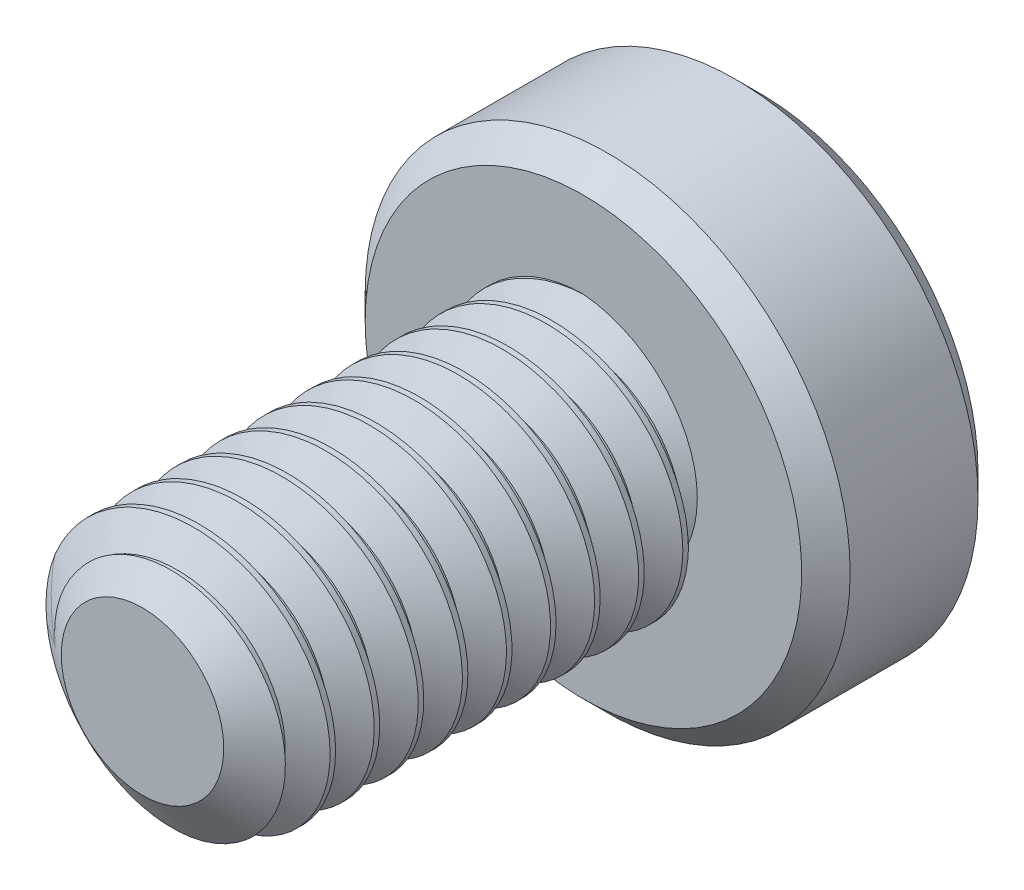
SolidWorks part; units mm, degrees
other "DetailItem1"
ref_plane "Front Plane" through (0, 0, 0) normal (0, 0, 1) x (1, 0, 0)
ref_plane "Top Plane" through (0, 0, 0) normal (0, 1, 0) x (1, 0, 0)
ref_plane "Right Plane" through (0, 0, 0) normal (1, 0, 0) x (0, 0, -1)
sketch "Sketch1" plane through (0, 0, 0) normal (0, 0, 1) x (1, 0, 0)
  circle A0 centre (0, 0) radius 1.5
  dimension "OD" = 3
extrude "Extrude1" add sketch "Sketch1" against normal blind 5
sketch "Sketch2" plane through (0, 0, 0) normal (0, 0, 1) x (1, 0, 0)
  circle A0 centre (0, 0) radius 1.5 construction
  circle A1 centre (0, 0) radius 1.5
curve "Helix/Spiral1" pitch 0.5 height 5.5 radius 1.5 centre (0, 0, 0) axis (0, 0, -1) start towards (0, 1, 0) parameters "pitch"=0.5
sketch "Sketch3" plane through (0, 0, 0) normal (1, 0, 0) x (0, 0, -1)
  line L0 (-0.4375, 1.5) -> (-0.25, 1.1752)
  line L1 (-0.25, 1.1752) -> (-0.1875, 1.1752)
  line L2 (-0.1875, 1.1752) -> (0, 1.5)
  line L3 (-0.4375, 1.5) -> (0, 1.5)
  line L4 (-0.2188, 1.5) -> (-0.2188, 1.1752) construction
  line L5 (-0.3438, 1.3376) -> (-0.0938, 1.3376) construction
  line L6 (0, 1.5) -> (0, -1.5) construction
  dimension "D1" = 0.0625
  dimension "D2" = 0.25
  dimension "D3" = 60
sweep "Cut-Sweep1" cut profiles "Sketch3" path "Helix/Spiral1"
sketch "Sketch4" plane through (0, 0, 0) normal (1, 0, 0) x (0, 0, -1)
  line L0 (0.4053, 1.5) -> (0, 0.9212)
  line L1 (0, 0.9212) -> (0, 1.5)
  line L2 (0.4053, 1.5) -> (0, 1.5)
  line L3 (-0.4375, 1.5) -> (0, 1.5) construction
  line L4 (0, 0) -> (7.0209, 0) construction
  dimension "D1" = 55
  dimension "D2" = 0.254
revolve "Cut-Revolve1" cut sketch "Sketch4" angle 360 about L4
sketch "Sketch6" plane through (0, 0, -5) normal (0, 0, -1) x (-1, 0, 0)
  circle A0 centre (0, 0) radius 2.75
  dimension "head dia" = 5.5
extrude "Extrude2" add sketch "Sketch6" along normal blind 2
sketch "Sketch7" plane through (0, 0, -7) normal (0, 0, -1) x (-1, 0, 0)
  line L1 (0, 1.1547) -> (-1, 0.5774)
  line L2 (-1, 0.5774) -> (-1, -0.5774)
  line L3 (-1, -0.5774) -> (0, -1.1547)
  line L4 (0, -1.1547) -> (1, -0.5774)
  line L5 (1, -0.5774) -> (1, 0.5774)
  line L6 (1, 0.5774) -> (0, 1.1547)
  circle A0 centre (0, 0) radius 1 construction
  dimension "hex dia" = 2
extrude "Cut-Extrude1" cut sketch "Sketch7" against normal blind 1.5
sketch "Sketch8" plane through (0, 0, -7) normal (0, 0, -1) x (-1, 0, 0)
  circle A0 centre (0, 0) radius 1.1547
extrude "Cut-Extrude2" cut sketch "Sketch8" against normal through all draft 45
chamfer "Chamfer1" distance 0.275 angle 45 2 edges at (-2.75, 0, -7) (-2.75, 0, -5)
sketch "Sketch10" plane through (0, 0, -5) normal (0, 0, 1) x (1, 0, 0)
  circle A1 centre (0, 0) radius 1.5
  circle A2 centre (0, 0) radius 1.5
  dimension "D1" = 0
ref_plane "Plane1" through (0, 0, -30) normal (0, 0, 1) x (1, 0, 0)
extrude "partial thread" [suppressed] add sketch "Sketch10" along normal up to surface (20 mm away) separate body up to plane "Plane1"
chamfer "Chamfer2" [suppressed] distance 0.06 angle 45
combine bodies "Combine1" [suppressed] operation type add bodies to combine 107 108
sketch "Sketch9" plane through (0, 0, 0) normal (1, 0, 0) x (0, 0, -1)
  line L0 (0, 1.5) -> (0, -1.5) construction
  line L1 (1.25, 1.5) -> (1.25, -1.5) construction
  dimension "D1" = 1.25
equation "\"D3@Helix/Spiral1\" = \"screw length@Extrude1\"+\"pitch@Helix/Spiral1\""
equation "\"D1@Sketch3\" = \"pitch@Helix/Spiral1\"*.125"
equation "\"D2@Sketch3\" = \"pitch@Helix/Spiral1\"*.5"
equation "\"D1@Cut-Extrude1\" = \"hex dia@Sketch7\"*.75"
equation "\"D1@Chamfer1\" = \"head dia@Sketch6\"*.05"
equation "\"D1@Sketch9\" = \"pitch@Helix/Spiral1\"*2.5"
equation "\"D1@Chamfer2\"=\"OD@Sketch1\"*.02"
